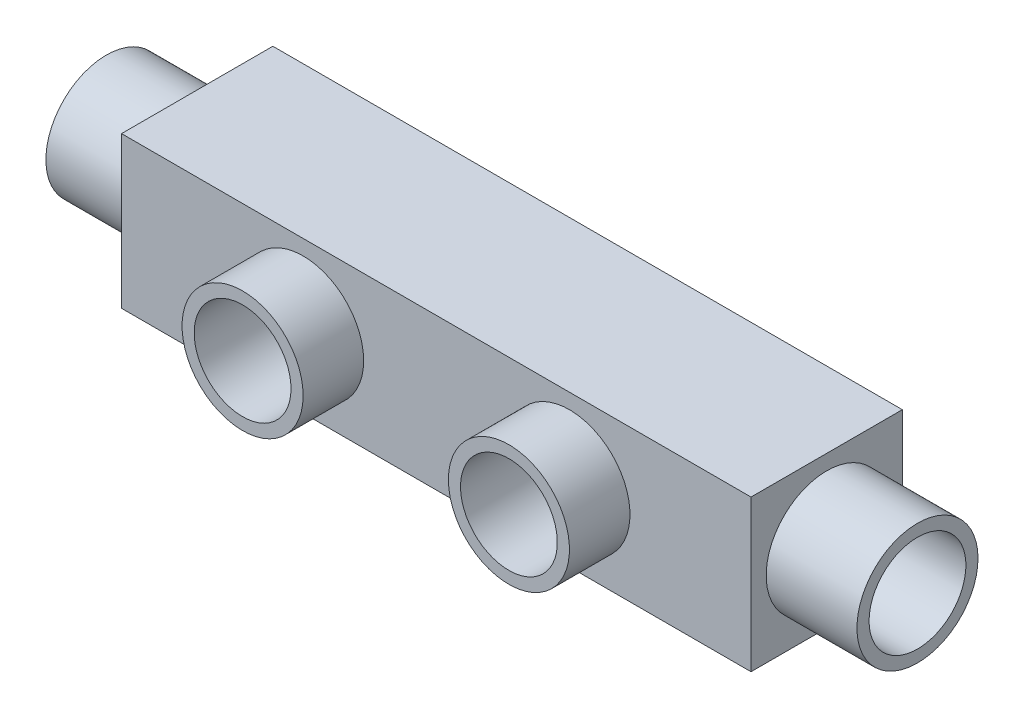
SolidWorks part; units mm, degrees
ref_plane "Płaszczyzna przednia" through (0, 0, 0) normal (0, 0, 1) x (1, 0, 0)
ref_plane "Płaszczyzna górna" through (0, 0, 0) normal (0, 1, 0) x (1, 0, 0)
ref_plane "Płaszczyzna prawa" through (0, 0, 0) normal (1, 0, 0) x (0, 0, -1)
sketch "Szkic1" plane through (0, 0, 0) normal (0, 0, 1) x (1, 0, 0)
  line L0 (52, 25) -> (52, 0)
  line L1 (0, 0) -> (104, 0)
  line L2 (0, 0) -> (0, 25)
  line L3 (0, 25) -> (104, 25)
  line L4 (104, 0) -> (104, 25)
  line L5 (49.5, 25) -> (49.5, 0)
  line L6 (54.5, 0) -> (54.5, 25)
  line L7 (52, 12.5) -> (30, 12.5) construction
  circle A0 centre (30, 12.5) radius 10
  circle A1 centre (74, 12.5) radius 10
  point P5 (0, 0)
  point P17 (0, 0)
  point P18 (0, 0)
  dimension "D1" = 20
  dimension "D2" = 5
  dimension "D3" = 44
  dimension "D4" = 25
  dimension "D5" = 104
extrude "Dodanie-wyciągnięcie1" add sketch "Szkic1" along normal blind 25 contours L5 L3 L2 L1 A0 | A0 | L0 L7 L5 L1 | L7 L0 L3 L5 region at (50.75, 18.75, 0) region at (50.75, 6.25, 0) region at (20.2828, 12.5, 0) region at (48.9455, 18.75, 0)
extrude "Dodanie-wyciągnięcie2" add sketch "Szkic1<3>" along normal blind 35 contours A0 region at (30, 12.5, 0)
sketch "Szkic1<3>" plane through (0, 0, 0) normal (0, 0, 1) x (1, 0, 0) same geometry as "Szkic1"
sketch "Szkic2" plane through (0, 0, 0) normal (1, 0, 0) x (0, 0, -1)
  line L0 (-25, 0) -> (0, 25) construction
  circle A0 centre (-12.5, 12.5) radius 10
  point P6 (0, 0)
  point P7 (0, 0)
  point P8 (-25, 0)
  point P10 (0, 25)
  dimension "D1" = 20
extrude "Dodanie-wyciągnięcie3" add sketch "Szkic2" against normal blind 15
sketch "Szkic3" plane through (-15, 0, 0) normal (-1, 0, 0) x (0, 0, 1)
  circle A0 centre (12.5, 12.5) radius 8
  dimension "D1" = 16
extrude "Wytnij-wyciągnięcie1" cut sketch "Szkic3" against normal blind 50
sketch "Szkic4" plane through (0, 0, 35) normal (0, 0, 1) x (1, 0, 0)
  circle A0 centre (30, 12.5) radius 8
  dimension "D1" = 16
extrude "Wytnij-wyciągnięcie2" cut sketch "Szkic4" against normal blind 31
mirror "Lustro1" about plane through (52, 0, 25) normal (1, 0, 0) of bodies 108
